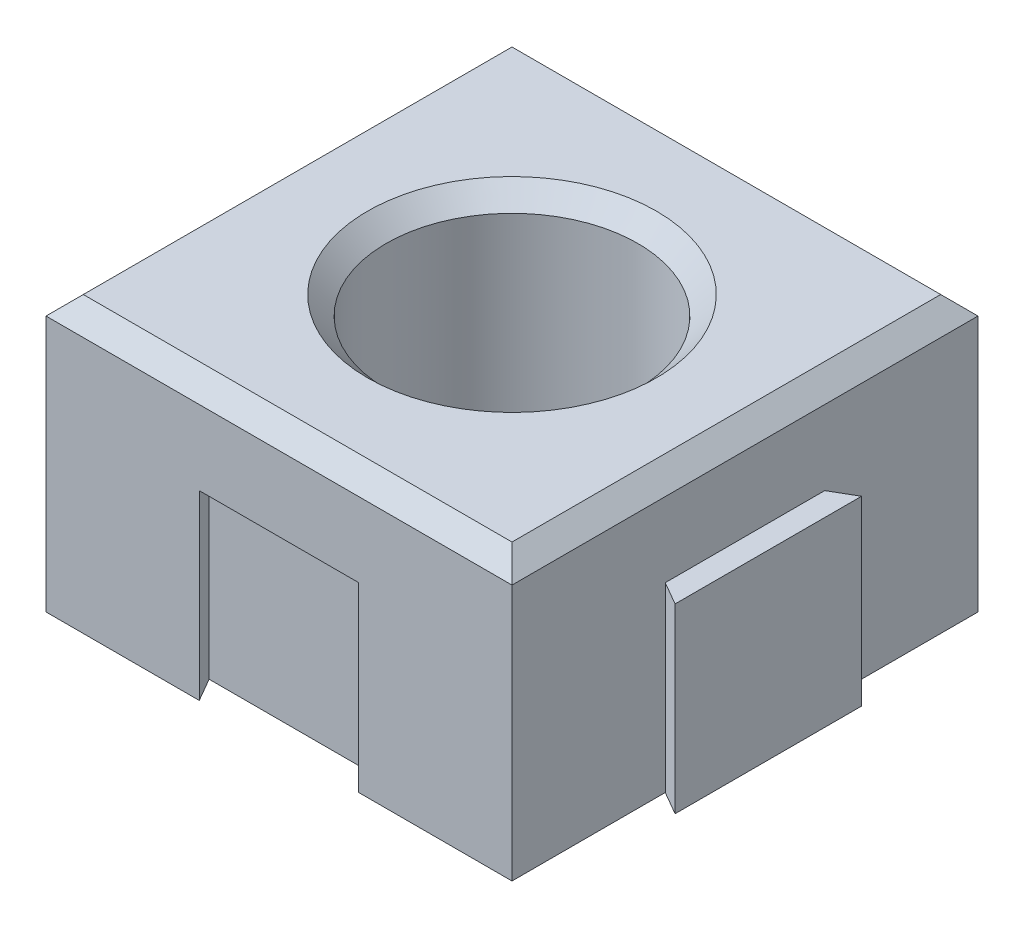
SolidWorks part; units mm, degrees
ref_plane "Front Plane" through (0, 0, 0) normal (0, 0, 1) x (1, 0, 0)
ref_plane "Top Plane" through (0, 0, 0) normal (0, 1, 0) x (1, 0, 0)
ref_plane "Right Plane" through (0, 0, 0) normal (1, 0, 0) x (0, 0, -1)
sketch "Sketch1" plane through (0, 0, 0) normal (0, 1, 0) x (1, 0, 0)
  line L1 (0, 0) -> (50, 0)
  line L2 (0, 0) -> (0, 50)
  line L3 (0, 50) -> (50, 50)
  line L4 (50, 0) -> (50, 50)
  dimension "D1" = 50
extrude "Boss-Extrude1" add sketch "Sketch1" along normal blind 30
sketch "Sketch2" plane through (0, 30, 0) normal (0, 1, 0) x (1, 0, 0)
  line L0 (0, 0) -> (50, 50) construction
  line L1 (0, 50) -> (50, 0) construction
  circle A0 centre (25, 25) radius 13.5
  dimension "D1" = 27
extrude "Cut-Extrude1" cut sketch "Sketch2" against normal blind 26
sketch "Sketch3" plane through (0, 0, 0) normal (0, 1, 0) x (1, 0, 0)
  line L0 (50, 33.5566) -> (52.5, 35)
  line L1 (50, 0) -> (50, 50) construction
  line L2 (52.5, 35) -> (52.5, 15)
  line L3 (52.5, 15) -> (50, 16.4434)
  line L4 (50, 25) -> (52.5, 25) construction
  line L5 (16.4434, 50) -> (15, 52.5)
  line L6 (50, 50) -> (0, 50) construction
  line L7 (15, 52.5) -> (35, 52.5)
  line L8 (35, 52.5) -> (33.5566, 50)
  line L9 (25, 52.5) -> (25, 50) construction
  line L10 (0, 33.5566) -> (2.5, 35)
  line L11 (0, 50) -> (0, 0) construction
  line L12 (2.5, 35) -> (2.5, 15)
  line L13 (2.5, 15) -> (0, 16.4434)
  line L14 (0, 25) -> (2.5, 25) construction
  line L15 (16.4434, 0) -> (15, 2.5)
  line L16 (0, 0) -> (50, 0) construction
  line L17 (15, 2.5) -> (35, 2.5)
  line L18 (35, 2.5) -> (33.5566, 0)
  line L19 (25, 0) -> (25, 2.5) construction
  line L20 (50, 16.4434) -> (50, 33.5566)
  line L21 (33.5566, 50) -> (16.4434, 50)
  line L22 (0, 33.5566) -> (0, 16.4434)
  line L23 (16.4434, 0) -> (33.5566, 0)
  point P8 (50, 25)
  dimension "D2" = 60
  dimension "D3" = 2.5
  dimension "D4" = 20
extrude "Boss-Extrude2" add sketch "Sketch3" along normal blind 20 contours L2 L3 L20 L0
extrude "Boss-Extrude3" add sketch "Sketch3<3>" along normal blind 20 contours L7 L8 L21 L5
sketch "Sketch3<3>" plane through (0, 0, 0) normal (0, 1, 0) x (1, 0, 0) same geometry as "Sketch3"
extrude "Cut-Extrude2" cut sketch "Sketch3<4>" along normal blind 20 contours L12 L13 L22 L10
sketch "Sketch3<4>" plane through (0, 0, 0) normal (0, 1, 0) x (1, 0, 0) same geometry as "Sketch3"
extrude "Cut-Extrude3" cut sketch "Sketch3<5>" along normal blind 20 contours L17 L18 L23 L15
sketch "Sketch3<5>" plane through (0, 0, 0) normal (0, 1, 0) x (1, 0, 0) same geometry as "Sketch3"
chamfer "Chamfer1" distance 2 angle 45 5 edges at (25, 30, -50) (50, 30, -25) (25, 30, 0) (0, 30, -25) (25, 30, -11.5)
sketch "Sketch4" plane through (0, 0, 0) normal (0, 1, 0) x (1, 0, 0)
  line L0 (12.5, 12.5) -> (37.5, 37.5) construction
  line L1 (12.5, 12.5) -> (37.5, 12.5) construction
  line L2 (12.5, 12.5) -> (12.5, 37.5) construction
  line L3 (12.5, 37.5) -> (37.5, 37.5) construction
  line L4 (37.5, 12.5) -> (37.5, 37.5) construction
  line L5 (12.5, 37.5) -> (37.5, 12.5) construction
  line L6 (0, 0) -> (12.5, 12.5) construction
  line L7 (12.5, 37.5) -> (0, 50) construction
  line L8 (50, 50) -> (37.5, 37.5) construction
  line L9 (50, 0) -> (37.5, 12.5) construction
  line L10 (0, 25) -> (25, 25) construction
  circle A0 centre (12.5, 37.5) radius 3.1
  circle A1 centre (37.5, 37.5) radius 3.1
  circle A2 centre (37.5, 12.5) radius 3.1
  circle A3 centre (12.5, 12.5) radius 3.1
  point P15 (12.5, 25)
  dimension "D1" = 6.2
extrude "Cut-Extrude4" cut sketch "Sketch4" along normal blind 4
chamfer "Chamfer2" distance 1 angle 45 4 edges at (37.5, 4, -9.4) (12.5, 4, -9.4) (12.5, 4, -34.4) (37.5, 4, -34.4)
chamfer "Chamfer3" distance 0.5 angle 45 24 edges at (25, 0, -2.5) (34.2783, 0, -1.25) (41.7783, 0, 0) (50, 0, -8.2217) (51.25, 0, -15.7217) (52.5, 0, -25) (51.25, 0, -34.2783) (50, 0, -41.7783) (41.7783, 0, -50) (34.2783, 0, -51.25) (25, 0, -52.5) (15.7217, 0, -51.25) (8.2217, 0, -50) (0, 0, -41.7783) (1.25, 0, -34.2783) (2.5, 0, -25) (1.25, 0, -15.7217) (0, 0, -8.2217) (8.2217, 0, 0) (15.7217, 0, -1.25) (12.5, 0, -34.4) (37.5, 0, -34.4) (37.5, 0, -9.4) (12.5, 0, -9.4)
